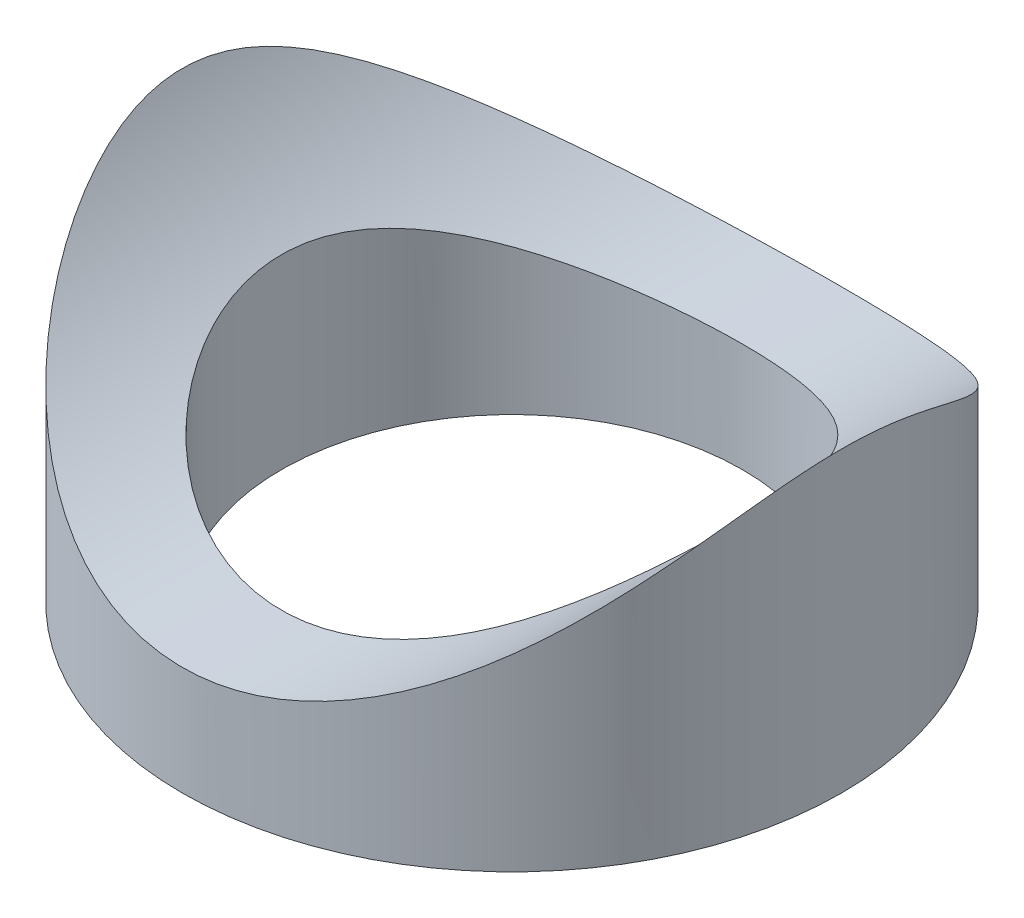
SolidWorks part; units mm, degrees
material "PTFE (general)"
ref_plane "Front Plane" through (0, 0, 0) normal (0, 0, 1) x (1, 0, 0)
ref_plane "Top Plane" through (0, 0, 0) normal (0, 1, 0) x (1, 0, 0)
ref_plane "Right Plane" through (0, 0, 0) normal (1, 0, 0) x (0, 0, -1)
sketch "Sketch1" plane through (0, 0, 0) normal (0, 1, 0) x (1, 0, 0)
  circle A0 centre (0, 0) radius 7.15
  circle A1 centre (0, 0) radius 5
  dimension "D1" = 10
  dimension "D2" = 14.3
extrude "Boss-Extrude1" add sketch "Sketch1" along normal blind 10
sketch "Sketch2" plane through (0, 0, 0) normal (0, 0, 1) x (1, 0, 0)
  line L0 (0, -5.5) -> (0, 5.5) construction
  circle A0 centre (0, 9.64) radius 8.28
  dimension "D2" = 16.56
  dimension "D3" = 9.64
  dimension "D1" = 0
extrude "Cut-Extrude1" cut sketch "Sketch2" against normal through all both and the other way through all
sketch "Sketch3" plane through (0, 0, 0) normal (0, -1, 0) x (1, 0, 0)
  circle A0 centre (0, 0) radius 7.15
  circle A1 centre (0, 0) radius 5
  circle A2 centre (0, 0) radius 7.15 construction
  dimension "D1" = 0
extrude "Boss-Extrude2" add sketch "Sketch3" along normal blind 1
